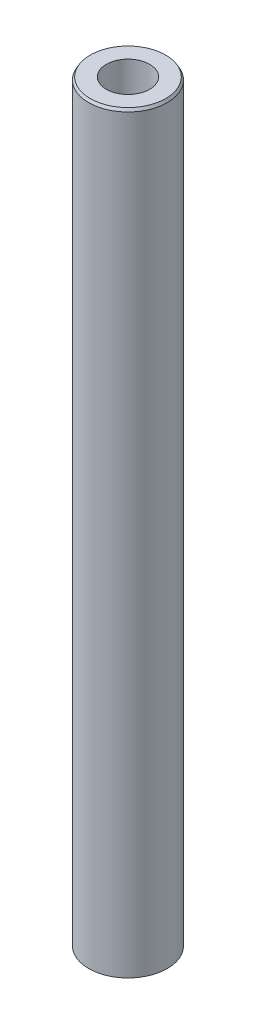
SolidWorks part; units mm, degrees
ref_plane "Front Plane" through (0, 0, 0) normal (0, 0, 1) x (1, 0, 0)
ref_plane "Top Plane" through (0, 0, 0) normal (0, 1, 0) x (1, 0, 0)
ref_plane "Right Plane" through (0, 0, 0) normal (1, 0, 0) x (0, 0, -1)
sketch "Sketch1" plane through (0, 0, 0) normal (0, 1, 0) x (1, 0, 0)
  circle A0 centre (0, 0) radius 7.5
  dimension "SHAFT_OD" = 15
extrude "Boss-Extrude1" add sketch "Sketch1" along normal blind 143.9534
sketch "Sketch2" plane through (0, 0, 0) normal (0, 1, 0) x (1, 0, 0)
  circle A0 centre (0, 0) radius 4.139
  dimension "BORE_D" = 8.2779
extrude "Cut-Extrude1" cut sketch "Sketch2" along normal through all
chamfer "Chamfer1" distance 0.519 angle 30 2 edges at (0, 143.9534, 7.5) (0, 0, 7.5) first distance on face at (0, 143.9534, 7.5) first distance on face at (0, 0, 4.139)
